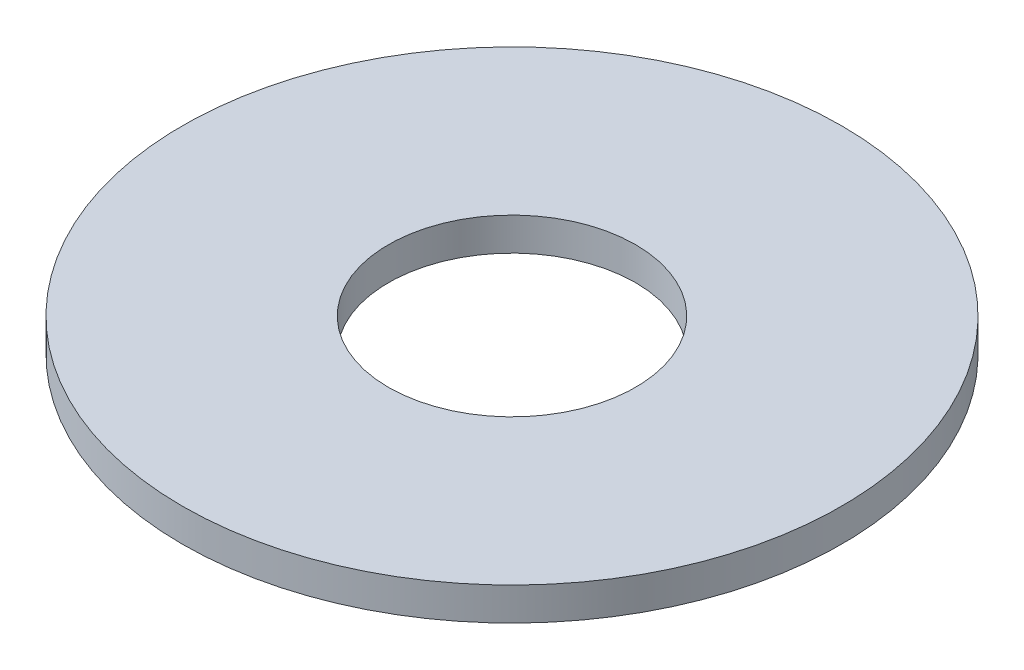
SolidWorks part; units mm, degrees
ref_plane "Front Plane" through (0, 0, 0) normal (0, 0, 1) x (1, 0, 0)
ref_plane "Top Plane" through (0, 0, 0) normal (0, 1, 0) x (1, 0, 0)
ref_plane "Right Plane" through (0, 0, 0) normal (1, 0, 0) x (0, 0, -1)
sketch "Sketch1" plane through (0, 0, 0) normal (0, 1, 0) x (1, 0, 0)
  circle A0 centre (0, 0) radius 40
  dimension "FLANGE_OD" = 80
extrude "Boss-Extrude1" add sketch "Sketch1" along normal blind 4
sketch "Sketch2" plane through (0, 0, 0) normal (0, 1, 0) x (1, 0, 0)
  circle A0 centre (0, 0) radius 15
  dimension "BORE_D" = 30
extrude "Cut-Extrude1" cut sketch "Sketch2" along normal through all
sketch "Sketch3" plane through (0, 4, 0) normal (0, 1, 0) x (1, 0, 0)
  circle A0 centre (0, 0) radius 10.3074 construction
  circle A1 centre (-10.3074, 0) radius 1.5731
  dimension "BOLT_D" = 3.1461
  dimension "BOLT_PCD" = 20.6147
extrude "Cut-Extrude2" cut sketch "Sketch3" against normal blind 2.9767 rebuild error yes
pattern_circular "CirPattern1" count 5 over 360 rebuild error yes
